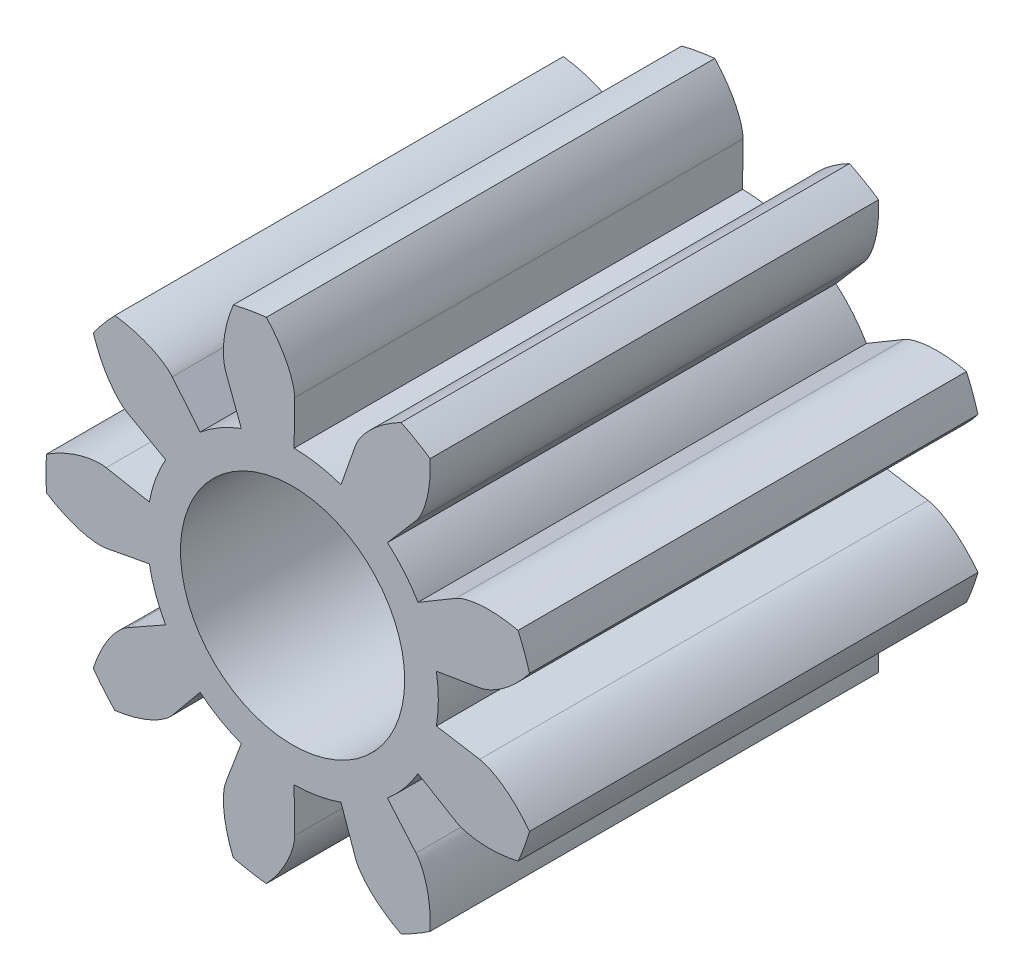
SolidWorks part; units mm, degrees
ref_plane "前视基准面" through (0, 0, 0) normal (0, 0, 1) x (1, 0, 0)
ref_plane "上视基准面" through (0, 0, 0) normal (0, 1, 0) x (1, 0, 0)
ref_plane "右视基准面" through (0, 0, 0) normal (1, 0, 0) x (0, 0, -1)
other "Configuration Table"
sketch "草图1" plane through (0, 0, 0) normal (0, 0, 1) x (1, 0, 0)
  line L0 (0, 0) -> (1.8, 0) construction
  line L1 (0, 0) -> (1.7727, 0.3126) construction
  line L2 (0, 0) -> (1.6688, 0.276)
  line L3 (1.7727, 0.3126) -> (1.7727, -0.3126) construction
  line L4 (0, 0) -> (1.6688, -0.276)
  circle A0 centre (0, 0) radius 2.2
  circle A1 centre (0, 0) radius 1.8 construction
  circle A2 centre (0, 0) radius 1.3
  circle A3 centre (0, 0) radius 1.6914 construction
  circle A4 centre (0, 0) radius 1
  spline S0 degree 4 poles (1.6688, 0.276) (1.6815, 0.2781) (1.7165, 0.2867) (1.7804, 0.3134) (1.8769, 0.3705) (1.9892, 0.4631) (2.115, 0.6012) (2.2366, 0.7836) (2.3401, 1.0009) (2.4181, 1.2482) (2.465, 1.503) (2.4828, 1.7615) (2.473, 2.0332) (2.4258, 2.3665) (2.3192, 2.7541) (2.1304, 3.1816) (1.8506, 3.6185) (1.5097, 4.0103) (1.1213, 4.3527) (0.6893, 4.6421) (0.2307, 4.8777) (-0.2607, 5.0574) (-0.7542, 5.1833) (-1.2841, 5.2523) (-1.6863, 5.2693) (-2.1385, 5.2469) (-2.3948, 5.2166) (-2.6865, 5.1734) (-2.8298, 5.138) (-2.9571, 5.1118) (-2.9949, 5.1006) (-3.0222, 5.094) (-3.037, 5.0905) knots 0 0 0 0 0 0.005604 0.015718 0.02996 0.048734 0.068727 0.096889 0.125051 0.153212 0.181374 0.209535 0.237696 0.271429 0.327752 0.384075 0.440398 0.496721 0.553044 0.609367 0.66569 0.722013 0.778336 0.834659 0.890982 0.909091 0.954545 0.977273 0.988636 0.994318 1 1 1 1 1 construction
  spline S1 degree 4 poles (1.6688, 0.276) (1.6815, 0.2781) (1.7165, 0.2867) (1.7804, 0.3134) (1.8769, 0.3705) (1.9892, 0.4631) (2.115, 0.6012) (2.2366, 0.7836) (2.3401, 1.0009) (2.4181, 1.2482) (2.465, 1.503) (2.4828, 1.7615) (2.473, 2.0332) (2.4258, 2.3665) (2.3192, 2.7541) (2.1304, 3.1816) (1.8506, 3.6185) (1.5097, 4.0103) (1.1213, 4.3527) (0.6893, 4.6421) (0.2307, 4.8777) (-0.2607, 5.0574) (-0.7542, 5.1833) (-1.2841, 5.2523) (-1.6863, 5.2693) (-2.0219, 5.2526) (-2.1774, 5.2392) (-2.215, 5.2356) knots 0 0 0 0 0 0.005604 0.015718 0.02996 0.048734 0.068727 0.096889 0.125051 0.153212 0.181374 0.209535 0.237696 0.271429 0.327752 0.384075 0.440398 0.496721 0.553044 0.609367 0.66569 0.722013 0.778336 0.834659 0.890982 0.909091 0.909091 0.909091 0.909091 0.909091
  spline S2 degree 4 poles (1.6688, -0.276) (1.6815, -0.2781) (1.7165, -0.2867) (1.7804, -0.3134) (1.8769, -0.3705) (1.9892, -0.4631) (2.115, -0.6012) (2.2366, -0.7836) (2.3401, -1.0009) (2.4181, -1.2482) (2.465, -1.503) (2.4828, -1.7615) (2.473, -2.0332) (2.4258, -2.3665) (2.3192, -2.7541) (2.1304, -3.1816) (1.8506, -3.6185) (1.5097, -4.0103) (1.1213, -4.3527) (0.6893, -4.6421) (0.2307, -4.8777) (-0.2607, -5.0574) (-0.7542, -5.1833) (-1.2841, -5.2523) (-1.6863, -5.2693) (-2.1385, -5.2469) (-2.3948, -5.2166) (-2.6865, -5.1734) (-2.8298, -5.138) (-2.9571, -5.1118) (-2.9949, -5.1006) (-3.0222, -5.094) (-3.037, -5.0905) knots 0 0 0 0 0 0.005604 0.015718 0.02996 0.048734 0.068727 0.096889 0.125051 0.153212 0.181374 0.209535 0.237696 0.271429 0.327752 0.384075 0.440398 0.496721 0.553044 0.609367 0.66569 0.722013 0.778336 0.834659 0.890982 0.909091 0.954545 0.977273 0.988636 0.994318 1 1 1 1 1 construction
  spline S3 degree 4 poles (1.6688, -0.276) (1.6815, -0.2781) (1.7165, -0.2867) (1.7804, -0.3134) (1.8769, -0.3705) (1.9892, -0.4631) (2.115, -0.6012) (2.2366, -0.7836) (2.3401, -1.0009) (2.4181, -1.2482) (2.465, -1.503) (2.4828, -1.7615) (2.473, -2.0332) (2.4258, -2.3665) (2.3192, -2.7541) (2.1304, -3.1816) (1.8506, -3.6185) (1.5097, -4.0103) (1.1213, -4.3527) (0.6893, -4.6421) (0.2307, -4.8777) (-0.2607, -5.0574) (-0.7542, -5.1833) (-1.2841, -5.2523) (-1.6863, -5.2693) (-2.0219, -5.2526) (-2.1774, -5.2392) (-2.215, -5.2356) knots 0 0 0 0 0 0.005604 0.015718 0.02996 0.048734 0.068727 0.096889 0.125051 0.153212 0.181374 0.209535 0.237696 0.271429 0.327752 0.384075 0.440398 0.496721 0.553044 0.609367 0.66569 0.722013 0.778336 0.834659 0.890982 0.909091 0.909091 0.909091 0.909091 0.909091
  point P15 (1.7727, 0)
  dimension "齿顶圆直径" = 4.4
  dimension "分度圆直径" = 3.6
  dimension "齿根圆直径" = 2.6
  dimension "基圆直径" = 3.3829
  dimension "内孔直径" = 2
  dimension "渐近线镜像线夹角" = 10
extrude "凸台-拉伸1" add sketch "草图1" along normal blind 4 contours A0 | A4
extrude "切除-拉伸1" cut sketch "草图1<3>" along normal through all contours A2 S3 A0 S1 region at (1.8185, 0, 0)
sketch "草图1<3>" plane through (0, 0, 0) normal (0, 0, 1) x (1, 0, 0) same geometry as "草图1"
pattern_circular "阵列(圆周)1" count 9 every 40 about axis through (0, 0, 4) along (0, 0, 1) of "切除-拉伸1"
equation "\"m\"= 0.4'模数"
equation "\"z\" = 9'齿数"
equation "\"a\"= 20度'压力角"
equation "\"d\"= \"m\" * \"z\"'分度圆直径"
equation "\"da\"= ( \"z\" + 2 ) * \"m\"'齿顶圆直径"
equation "\"df\"= ( \"z\" - 2.5 ) * \"m\"'齿根圆直径"
equation "\"s\"= 0.5 * PI * \"m\"'分度圆齿厚"
equation "\"r\"= 0.38 * \"m\"'齿根圆角"
equation "\"B\"= 0.3 * \"d\"'齿厚"
equation "\"db\"= \"m\" * \"z\" * cos ( \"a\" )'基圆直径"
equation "\"rb\"= \"db\" / 2'基圆半径"
equation "\"齿顶圆直径@草图1\"= \"da\""
equation "\"分度圆直径@草图1\"= \"d\""
equation "\"齿根圆直径@草图1\"= \"df\""
equation "\"基圆直径@草图1\"= \"db\""
equation "\"渐近线镜像线夹角@草图1\"= 360 / 4 / \"z\""
equation "\"h\" = 4'齿轮厚度"
equation "\"ir\"= 2'内孔直径"
equation "\"内孔直径@草图1\"= \"ir\""
equation "\"齿轮厚@凸台-拉伸1\"= \"h\""
equation "\"齿轮夹角@阵列(圆周)1\"= 360 / \"z\""
equation "\"齿数@阵列(圆周)1\"= \"z\""
